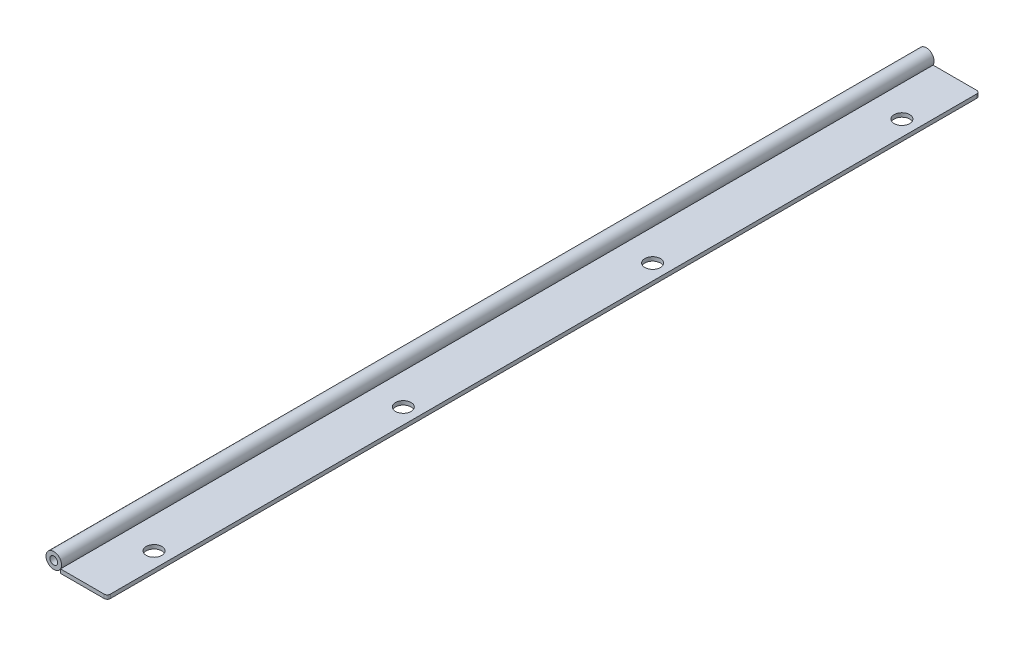
SolidWorks part; units mm, degrees
ref_plane "Front Plane" through (0, 0, 0) normal (0, 0, 1) x (1, 0, 0)
ref_plane "Top Plane" through (0, 0, 0) normal (0, 1, 0) x (1, 0, 0)
ref_plane "Right Plane" through (0, 0, 0) normal (1, 0, 0) x (0, 0, -1)
sketch "Sketch1" plane through (0, 0, 0) normal (0, 1, 0) x (1, 0, 0)
  line L1 (0, 0) -> (38.1, 0)
  line L2 (0, 0) -> (0, 711.2)
  line L3 (0, 711.2) -> (38.1, 711.2)
  line L4 (38.1, 0) -> (38.1, 711.2)
  dimension "D1" = 38.1
  dimension "D2" = 711.2
extrude "Boss-Extrude1" add sketch "Sketch1" along normal blind 3.175
sketch "Sketch2" plane through (0, 3.175, 0) normal (0, 1, 0) x (-1, 0, 0)
  line L0 (-38.1, 0) -> (-38.1, -711.2) construction
  line L1 (-38.1, -355.6) -> (0, -355.6) construction
  line L2 (0, -711.2) -> (0, 0) construction
  circle A0 centre (-25.4, -406.4) radius 3.175
  circle A1 centre (-25.4, -355.6) radius 3.175
  circle A2 centre (-25.4, -304.8) radius 3.175
  circle A3 centre (-25.4, -457.2) radius 3.175
  circle A4 centre (-25.4, -508) radius 3.175
  circle A5 centre (-25.4, -558.8) radius 3.175
  circle A6 centre (-25.4, -609.6) radius 3.175
  circle A7 centre (-25.4, -660.4) radius 3.175
  circle A8 centre (-25.4, -711.2) radius 3.175
  circle A9 centre (-25.4, -762) radius 3.175
  circle A10 centre (-25.4, -254) radius 3.175
  circle A11 centre (-25.4, -203.2) radius 3.175
  circle A12 centre (-25.4, -152.4) radius 3.175
  circle A13 centre (-25.4, -101.6) radius 3.175
  circle A14 centre (-25.4, -50.8) radius 3.175
  circle A15 centre (-25.4, 0) radius 3.175
  circle A16 centre (-25.4, 50.8) radius 3.175
  dimension "D4" = 6.35
  dimension "D3" = 50.8
  dimension "D1" = 12.7
  dimension "D2" = 12.7
  dimension "D5" = 8
  dimension "D6" = 8
extrude "Cut-Extrude1" cut sketch "Sketch2" against normal up to next rebuild error yes
fillet "Fillet1" radius 2.54 2 edges at (38.1, 1.5875, 0) (38.1, 1.5875, -711.2)
sketch "Sketch3" plane through (0, 0, 0) normal (0, 0, 1) x (1, 0, 0)
  line L0 (0, 0) -> (35.56, 0) construction
  circle A0 centre (-5.4993, 6.35) radius 6.35
  circle A1 centre (-5.4993, 6.35) radius 3.175
  dimension "D1" = 12.7
  dimension "D2" = 6.35
extrude "Boss-Extrude2" add sketch "Sketch3" against normal blind 711.2 separate body
sketch "Sketch4" plane through (0, 0, 0) normal (0, -1, 0) x (-1, 0, 0)
  line L0 (-35.56, 711.2) -> (0, 711.2) construction
  line L1 (0, 711.2) -> (0, 0) construction
  circle A0 centre (-25.4, 660.4) radius 6.35
  circle A1 centre (-25.4, 457.2) radius 6.35
  circle A2 centre (-25.4, 254) radius 6.35
  circle A3 centre (-25.4, 50.8) radius 6.35
  dimension "D1" = 50.8
  dimension "D2" = 25.4
  dimension "D3" = 203.2
  dimension "D4" = 203.2
  dimension "D5" = 203.2
extrude "Cut-Extrude2" cut sketch "Sketch4" against normal through all
